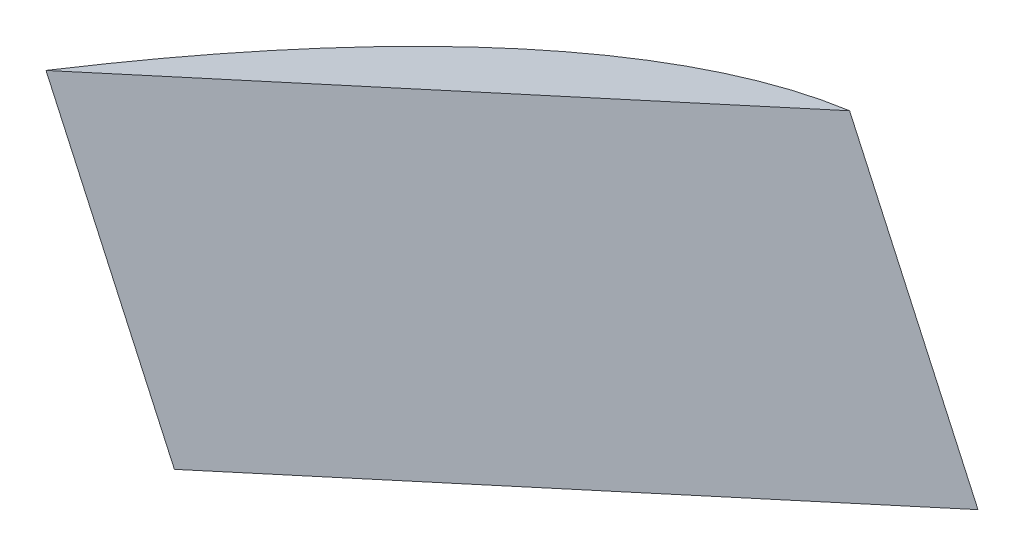
SolidWorks part; units mm, degrees
ref_plane "Front Plane" through (0, 0, 0) normal (0, 0, 1) x (1, 0, 0)
ref_plane "Top Plane" through (0, 0, 0) normal (0, 1, 0) x (1, 0, 0)
ref_plane "Right Plane" through (0, 0, 0) normal (1, 0, 0) x (0, 0, -1)
sketch "Sketch2" plane through (55.7758, -122.1656, 0) normal (0.4153, -0.9097, 0) x (0, 0, -1)
  line L0 (30, 119.1431) -> (30, -0.8569)
  line L1 (39.8265, 178.2862) -> (39.8265, -60) construction
  arc A0 (30, 119.1431) -> (30, -0.8569) centre (-148.265, 59.1431) cw
  point P7 (39.8265, 59.1431)
  point P8 (39.8265, -7.9879)
extrude "Boss-Extrude1" add sketch "Sketch2" against normal blind 21 and the other way blind 21
